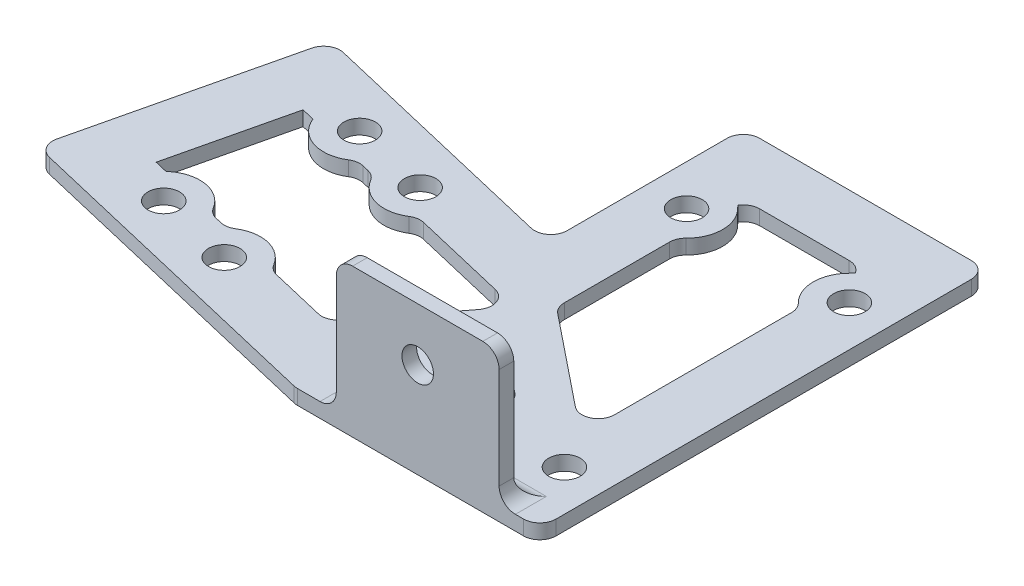
SolidWorks part; units mm, degrees
ref_plane "Front" through (0, 0, 0) normal (0, 0, 1) x (1, 0, 0)
ref_plane "Top" through (0, 0, 0) normal (0, 1, 0) x (1, 0, 0)
ref_plane "Right" through (0, 0, 0) normal (1, 0, 0) x (0, 0, -1)
sketch "Sketch1" plane through (0, 0, 0) normal (0, 1, 0) x (1, 0, 0)
  line L0 (-19.05, -34.925) -> (-10.2851, 2.1531) construction
  line L1 (-19.05, 34.925) -> (19.05, 34.925)
  line L2 (-19.05, 34.925) -> (-19.05, -34.925)
  line L3 (-19.05, -34.925) -> (19.05, -34.925)
  line L4 (19.05, 34.925) -> (19.05, -34.925)
  line L5 (-19.05, 34.925) -> (19.05, -34.925) construction
  line L6 (-19.05, -34.925) -> (19.05, 34.925) construction
  line L7 (-19.05, -34.925) -> (-71.8159, -22.4517)
  line L8 (-10.2851, 2.1531) -> (-63.051, 14.6264)
  line L9 (-71.8159, -22.4517) -> (-63.051, 14.6264)
  point P0 (0, 0)
  dimension "D1" = 38.1
  dimension "D2" = 69.85
  dimension "D3" = 13.3
  dimension "D4" = 38.1
extrude "Boss-Extrude1" add sketch "Sketch1" along normal blind 2.286
sketch "Sketch2" plane through (0, 2.286, 0) normal (0, 1, 0) x (1, 0, 0)
  line L0 (0, -34.925) -> (0, 25.4) construction
  line L3 (-19.05, -34.925) -> (19.05, -34.925) construction
  line L4 (-12.7, -32.639) -> (12.7, -32.639)
  line L5 (-12.7, -32.639) -> (-12.7, -34.925)
  line L6 (-12.7, -34.925) -> (12.7, -34.925)
  line L7 (12.7, -32.639) -> (12.7, -34.925)
  line L8 (-12.7, -32.639) -> (12.7, -34.925) construction
  line L9 (-12.7, -34.925) -> (12.7, -32.639) construction
  point P6 (0, -33.782)
  dimension "D1" = 25.4
  dimension "D2" = 2.286
extrude "Boss-Extrude2" add sketch "Sketch2" along normal blind 20.828
hole_wizard "#10 (0.1935) Diameter Hole1" positions "Sketch3" profile "Sketch4" hole size "#10" standard "ANSI Inch" end condition through all
sketch "Sketch3" plane through (0, 2.286, 0) normal (0, 1, 0) x (1, 0, 0)
  line L0 (0, 34.925) -> (0, -23.114) construction
  line L6 (-19.05, 34.925) -> (19.05, 34.925) construction
  line L7 (-19.05, -34.925) -> (-12.7, -34.925) construction
  line L8 (-12.7, -24.735) -> (-12.7, 19.715) construction
  line L9 (-12.7, 19.715) -> (12.7, 19.715) construction
  point P0 (-12.7, -24.735)
  point P10 (12.7, -24.735)
  point P28 (-12.7, 19.715)
  point P36 (12.7, 19.715)
  dimension "D1" = 25.4
  dimension "D2" = 10.19
  dimension "D3" = 25.4
  dimension "D4" = 44.45
sketch "Sketch4" plane through (-12.7, 2.286, 24.735) normal (1, 0, 0) x (0, 0, 1)
  line L0 (0, 0) -> (0, 2.286)
  line L1 (0, 2.286) -> (2.4574, 2.286)
  line L2 (2.4574, 2.286) -> (2.4574, 0)
  line L5 (2.4574, 0) -> (0, 0)
  line L11 (0, -6.35) -> (0, 107.95) construction
  dimension "Thru Hole Dia." = 4.9149
  dimension "Thru Hole Depth" = 2.286
hole_wizard "#10 (0.1935) Diameter Hole2" positions "Sketch5" profile "Sketch6" hole size "#10" standard "ANSI Inch" end condition through all
sketch "Sketch5" plane through (0, 0, 32.639) normal (0, 0, -1) x (-1, 0, 0)
  line L0 (0, 23.114) -> (0, 14.859) construction
  line L1 (-12.7, 23.114) -> (12.7, 23.114) construction
  point P0 (0, 14.859)
  dimension "D1" = 8.255
sketch "Sketch6" plane through (0, 14.859, 32.639) normal (1, 0, 0) x (0, 1, 0)
  line L0 (0, 0) -> (0, 2.286)
  line L1 (0, 2.286) -> (2.4574, 2.286)
  line L2 (2.4574, 2.286) -> (2.4574, 0)
  line L5 (2.4574, 0) -> (0, 0)
  line L11 (0, -6.35) -> (0, 107.95) construction
  dimension "Thru Hole Dia." = 4.9149
  dimension "Thru Hole Depth" = 2.286
hole_wizard "#10 (0.1935) Diameter Hole3" positions "Sketch7" profile "Sketch8" hole size "#10" standard "ANSI Inch" end condition through all
sketch "Sketch7" plane through (0, 2.286, 0) normal (0, 1, 0) x (1, 0, 0)
  line L0 (-64.5118, 8.4468) -> (-48.6853, 4.7055) construction
  line L1 (-71.8159, -22.4517) -> (-63.051, 14.6264) construction
  line L2 (-48.6853, 4.7055) -> (-36.326, 1.7839) construction
  line L4 (-19.05, 4.225) -> (-63.051, 14.6264) construction
  line L5 (-67.4335, -3.9126) -> (-39.2473, -10.5755) construction
  point P0 (-48.6853, 4.7055)
  point P8 (-36.326, 1.7839)
  point P18 (-54.5286, -20.0132)
  point P19 (-42.1692, -22.9348)
  dimension "D1" = 12.7
  dimension "D2" = 12.7
sketch "Sketch8" plane through (-48.6853, 2.286, -4.7055) normal (1, 0, 0) x (0, 0, 1)
  line L0 (0, 0) -> (0, 2.286)
  line L1 (0, 2.286) -> (2.4574, 2.286)
  line L2 (2.4574, 2.286) -> (2.4574, 0)
  line L5 (2.4574, 0) -> (0, 0)
  line L11 (0, -6.35) -> (0, 107.95) construction
  dimension "Thru Hole Dia." = 4.9149
  dimension "Thru Hole Depth" = 2.286
ref_plane "Plane1" through (-0.5524, -4.5962, -1.315) normal (0, 0, -1) x (-1, 0, 0)
sketch "Sketch10" plane through (0, 2.286, 0) normal (0, 1, 0) x (1, 0, 0)
  line L11 (-22.2363, -24.3782) -> (-9.525, -7.8141) construction
  line L12 (9.525, -23.114) -> (-9.525, -7.8141) construction
  line L13 (11.5132, -20.6385) -> (-10.0677, -3.306)
  line L14 (-25.6279, -23.5825) -> (-9.525, -2.5989)
  line L15 (7.5368, -25.5895) -> (-8.9823, -12.3221)
  line L16 (-19.7175, -26.3112) -> (-8.9823, -12.3221)
  line L17 (-24.7551, -22.4453) -> (-10.0677, -3.306) construction
  line L18 (11.5132, -20.6385) -> (-10.0677, -3.306) construction
  line L19 (-22.225, -24.3869) -> (-22.225, -23.114)
  line L20 (-22.225, -24.3869) -> (-22.225, -23.114)
  line L22 (9.525, -23.114) -> (9.525, 25.4)
  line L23 (9.525, 25.4) -> (-9.525, 25.4)
  line L24 (-9.525, 25.4) -> (-9.525, -7.8141)
  line L25 (-9.525, -7.8141) -> (-55.9727, 3.1657)
  line L26 (-55.9727, 3.1657) -> (-60.3552, -15.3734)
  line L27 (-60.3552, -15.3734) -> (-22.225, -24.3869)
  line L28 (-22.225, -23.114) -> (9.525, -23.114)
  line L29 (9.525, -23.114) -> (9.525, 25.4)
  line L30 (9.525, 25.4) -> (-9.525, 25.4)
  line L31 (-9.525, 25.4) -> (-9.525, -7.8141)
  line L32 (-9.525, -7.8141) -> (-55.9727, 3.1657)
  line L33 (-55.9727, 3.1657) -> (-60.3552, -15.3734)
  line L34 (-60.3552, -15.3734) -> (-22.225, -24.3869)
  line L35 (-22.225, -23.114) -> (9.525, -23.114)
  circle A5 centre (-42.1692, -22.9348) radius 5.6324
  circle A6 centre (-42.1692, -22.9348) radius 5.6324
  circle A8 centre (-54.5286, -20.0132) radius 5.6324
  circle A9 centre (-54.5286, -20.0132) radius 5.6324
  circle A11 centre (-48.6853, 4.7055) radius 5.6324
  circle A12 centre (-48.6853, 4.7055) radius 5.6324
  circle A14 centre (-36.326, 1.7839) radius 5.6324
  circle A15 centre (-36.326, 1.7839) radius 5.6324
  circle A17 centre (-12.7, 19.715) radius 5.6324
  circle A18 centre (-12.7, 19.715) radius 5.6324
  circle A20 centre (12.7, 19.715) radius 5.6324
  circle A21 centre (12.7, 19.715) radius 5.6324
  circle A23 centre (12.7, -24.735) radius 5.6324
  circle A24 centre (12.7, -24.735) radius 5.6324
  circle A26 centre (-12.7, -24.735) radius 5.6324
  circle A27 centre (-12.7, -24.735) radius 5.6324
  dimension "D1" = 3.175
  dimension "D2" = 3.175
  dimension "D3" = 3.175
  dimension "D4" = 3.175
  dimension "D5" = 3.175
  dimension "D6" = 3.175
  dimension "D7" = 9.525
  dimension "D8" = 3.175
  dimension "D9" = 3.175
  dimension "D10" = 3.175
  dimension "D11" = 3.175
extrude "Cut-Extrude1" cut sketch "Sketch10" against normal blind 50.8 contours A27 L35 A24 L29 A21 L30 L31 A18 L32 A15 A12 L33 A9 L34 A6 | A27 L35 L15 L16 | A21 L29 L30 L31 A18 L13
fillet "Fillet1" radius 2.54 27 edges at (-19.05, 1.143, 34.925) (-63.051, 1.143, -14.6264) (-19.05, 1.143, -4.225) (-19.05, 1.143, -34.925) (19.05, 1.143, -34.925) (19.05, 1.143, 34.925) (-71.8159, 1.143, 22.4517) (-14.3831, 1.143, 19.3599) (4.4546, 1.143, 23.114) (-7.3059, 1.143, 23.114) (-8.9823, 1.143, 12.3221) (9.525, 1.143, -15.0627) (9.525, 1.143, -24.3673) (9.525, 1.143, 19.0418) (-9.525, 1.143, 3.7418) (-9.525, 1.143, -24.3673) (-9.525, 1.143, -15.0627) (-9.525, 1.143, -25.4) (9.525, 1.143, -25.4) (-32.5288, 1.143, 2.3762) (-41.5839, 1.143, 0.2357) (-12.9126, 1.143, 7.0133) (-25.6279, 1.143, 23.5825) (-45.9663, 1.143, 18.7747) (-36.9113, 1.143, 20.9153) (-49.2707, 1.143, 17.9936) (-44.8882, 1.143, -0.5454)
fillet "Fillet2" radius 2.54 5 edges at (12.7, 2.286, 33.782) (0, 2.286, 32.639) (-12.7, 2.286, 33.782) (12.7, 23.114, 33.782) (-12.7, 23.114, 33.782)
